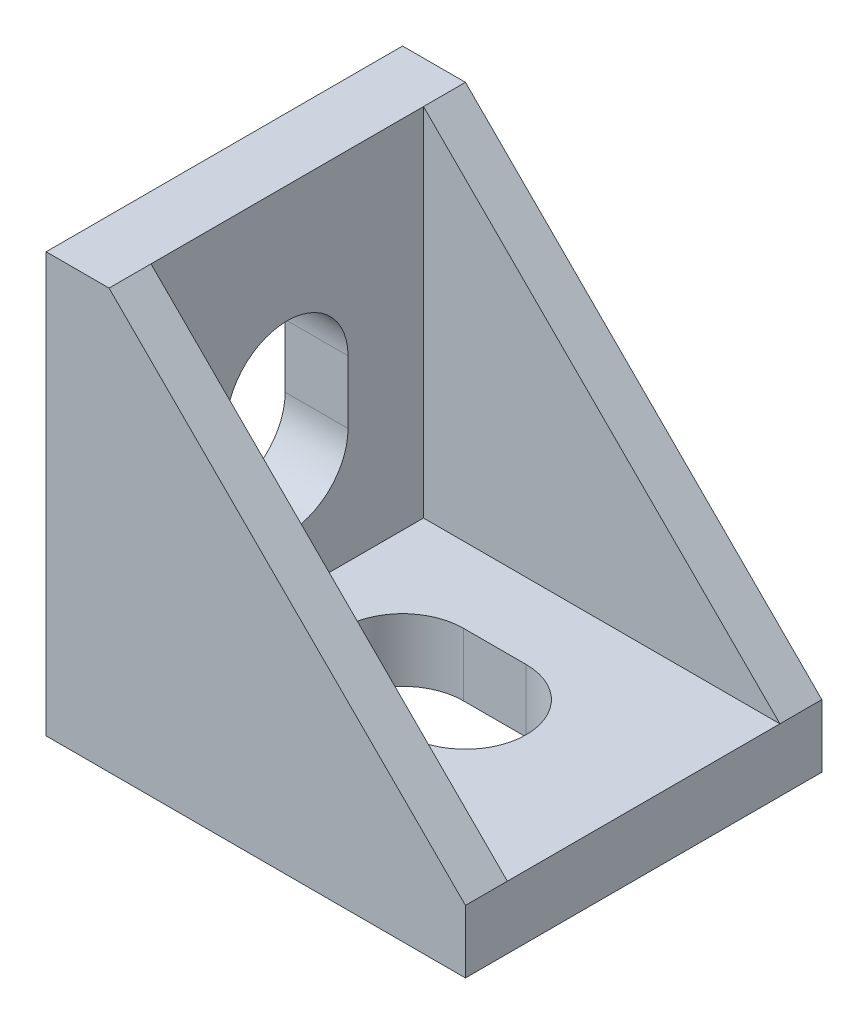
SolidWorks part; units mm, degrees
material "6061-T6 (SS)"
ref_plane "Front Plane" through (0, 0, 0) normal (0, 0, 1) x (1, 0, 0)
ref_plane "Top Plane" through (0, 0, 0) normal (0, 1, 0) x (1, 0, 0)
ref_plane "Right Plane" through (0, 0, 0) normal (1, 0, 0) x (0, 0, -1)
sketch "Sketch1" plane through (0, 0, 0) normal (0, 0, 1) x (1, 0, 0)
  line L0 (0, 20) -> (0, 0)
  line L1 (0, 0) -> (20, 0)
  line L2 (20, 0) -> (20, 3)
  line L3 (20, 3) -> (3, 20)
  line L4 (3, 20) -> (0, 20)
  line L5 (0, 0) -> (11.5, 11.5) construction
  dimension "D1" = 20
  dimension "D3" = 3
extrude "Boss-Extrude1" add sketch "Sketch1" along normal mid plane 17
sketch "Sketch2" plane through (0, 20, 0) normal (0, 1, 0) x (1, 0, 0)
  line L0 (3, -8.5) -> (3, 8.5) construction
  line L1 (3, 6.5) -> (20, 6.5)
  line L2 (3, 6.5) -> (3, -6.5)
  line L3 (3, -6.5) -> (20, -6.5)
  line L4 (20, 6.5) -> (20, -6.5)
  line L5 (20, -8.5) -> (20, 8.5) construction
  line L6 (20, 8.5) -> (3, 8.5) construction
  line L7 (3, 0) -> (0, 0) construction
  dimension "D1" = 2
extrude "Cut-Extrude1" cut sketch "Sketch2" against normal blind 17
sketch "Sketch3" plane through (3, 0, 0) normal (1, 0, 0) x (0, 0, -1)
  line L0 (0, 20) -> (0, 10) construction
  line L1 (6.5, 20) -> (-6.5, 20) construction
  line L2 (0, 8.5) -> (0, 11.5) construction
  line L3 (-2.9, 8.5) -> (-2.9, 11.5)
  line L4 (2.9, 8.5) -> (2.9, 11.5)
  line L5 (-8.5, 0) -> (8.5, 0) construction
  arc A0 (-2.9, 8.5) -> (2.9, 8.5) centre (0, 8.5) ccw
  arc A1 (2.9, 11.5) -> (-2.9, 11.5) centre (0, 11.5) ccw
  point P7 (0, 10)
  dimension "D1" = 5.8
  dimension "D2" = 3
  dimension "D3" = 8.5
extrude "Cut-Extrude2" cut sketch "Sketch3" against normal up to next
sketch "Sketch5" plane through (0, 3, 0) normal (0, 1, 0) x (1, 0, 0)
  line L0 (20, 0) -> (10, 0) construction
  line L2 (20, -6.5) -> (20, 6.5) construction
  line L3 (11.5, 0) -> (8.5, 0) construction
  line L4 (11.5, -2.9) -> (8.5, -2.9)
  line L6 (11.5, 2.9) -> (8.5, 2.9)
  line L7 (0, -8.5) -> (0, 8.5) construction
  arc A0 (11.5, -2.9) -> (11.5, 2.9) centre (11.5, 0) ccw
  arc A1 (8.5, 2.9) -> (8.5, -2.9) centre (8.5, 0) ccw
  point P7 (10, 0)
  dimension "D1" = 5.8
  dimension "D2" = 3
  dimension "D3" = 8.5
extrude "Cut-Extrude3" cut sketch "Sketch5" against normal through all
sketch "Sketch6" plane through (0, 0, 0) normal (0, 0, 1) x (1, 0, 0)
  line L0 (0, 20) -> (0, 0) construction
  line L1 (0, 18.5) -> (-1, 18.5)
  line L2 (0, 18.5) -> (0, 16.65)
  line L3 (0, 16.65) -> (-1, 16.65)
  line L4 (-1, 18.5) -> (-1, 16.65)
  line L5 (0, 10) -> (-1.5249, 10) construction
  line L6 (-1, 1.5) -> (-1, 3.35)
  line L7 (0, 3.35) -> (-1, 3.35)
  line L8 (0, 1.5) -> (0, 3.35)
  line L9 (0, 1.5) -> (-1, 1.5)
  line L10 (0, 0) -> (6.9595, 6.9595) construction
  line L11 (0, 0) -> (20, 0) construction
  line L12 (1.5, 0) -> (1.5, -1)
  line L13 (1.5, 0) -> (3.35, 0)
  line L14 (3.35, 0) -> (3.35, -1)
  line L15 (1.5, -1) -> (3.35, -1)
  line L16 (18.5, -1) -> (16.65, -1)
  line L17 (16.65, 0) -> (16.65, -1)
  line L18 (18.5, 0) -> (16.65, 0)
  line L19 (18.5, 0) -> (18.5, -1)
  dimension "D1" = 45
  dimension "D2" = 1.85
  dimension "D3" = 1
  dimension "D4" = 17
extrude "Boss-Extrude2" add sketch "Sketch6" along normal mid plane 4
sketch "Sketch7" plane through (0, 0, 0) normal (-1, 0, 0) x (0, 0, 1)
  line L0 (0, 0) -> (0, 10) construction
  dimension "D1" = 10
sketch "Sketch8" plane through (0, 0, 0) normal (0, -1, 0) x (1, 0, 0)
  line L0 (0, 0) -> (10, 0) construction
  line L1 (0, 8.5) -> (0, -8.5) construction
  dimension "D1" = 10
ref_axis "Axis1" through (0, 10, 0) along (1, 0, 0)
ref_axis "Axis2" through (10, 0, 0) along (0, 1, 0)
